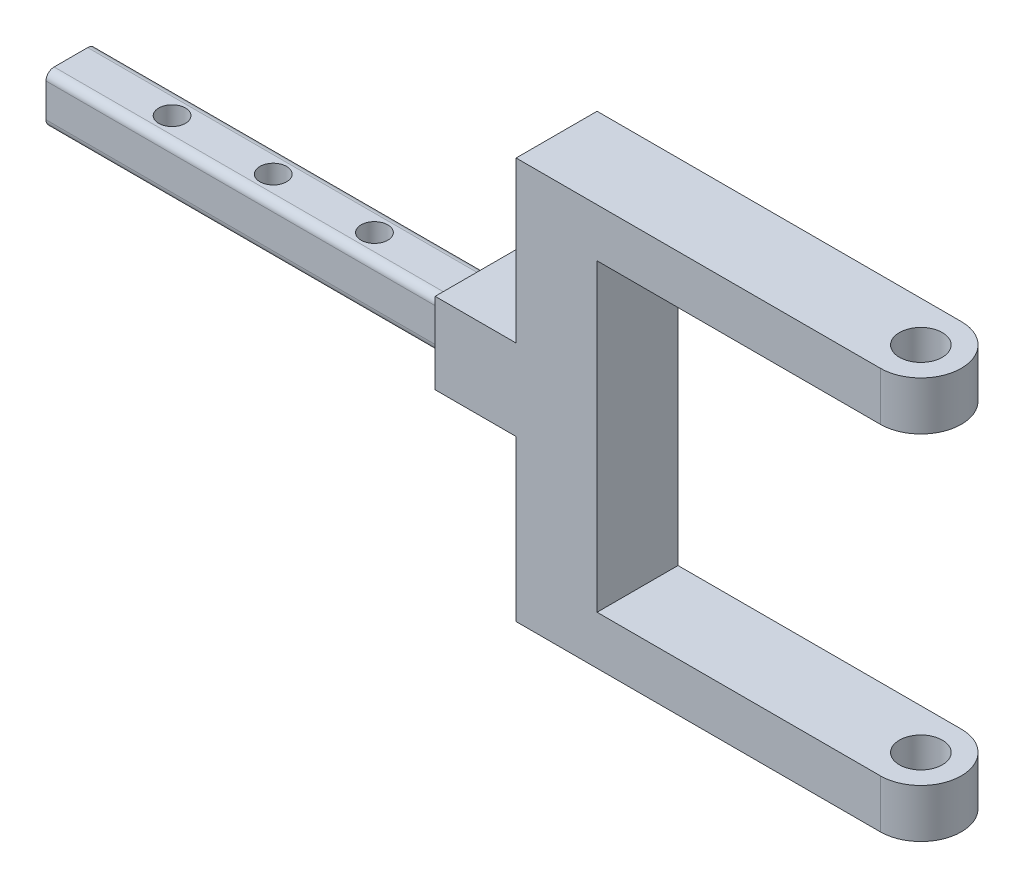
SolidWorks part; units mm, degrees
ref_plane "前视基准面" through (0, 0, 0) normal (0, 0, 1) x (1, 0, 0)
ref_plane "上视基准面" through (0, 0, 0) normal (0, 1, 0) x (1, 0, 0)
ref_plane "右视基准面" through (0, 0, 0) normal (1, 0, 0) x (0, 0, -1)
other "Configuration Table"
sketch "草图1" plane through (0, 0, 0) normal (0, 0, 1) x (1, 0, 0)
  line L0 (0, 18.8) -> (0, -18.8)
  line L1 (0, 18.8) -> (40, 18.8)
  line L2 (40, 18.8) -> (40, 24.8)
  line L3 (40, 24.8) -> (-10, 24.8)
  line L4 (-10, 24.8) -> (-10, -24.8)
  line L5 (-10, -24.8) -> (40, -24.8)
  line L6 (40, -24.8) -> (40, -18.8)
  line L7 (40, -18.8) -> (0, -18.8)
  point P4 (0, 0)
  dimension "D1" = 37.6
  dimension "D2" = 40
  dimension "D3" = 6
  dimension "D4" = 10
extrude "凸台-拉伸1" add sketch "草图1" along normal blind 10
sketch "草图2" plane through (-10, 0, 0) normal (-1, 0, 0) x (0, 0, 1)
  line L0 (8.075, 3.075) -> (8.075, -3.075)
  line L1 (1.925, -3.075) -> (8.075, -3.075)
  line L2 (1.925, 3.075) -> (1.925, -3.075)
  line L3 (1.925, 3.075) -> (8.075, 3.075)
  line L4 (5, 24.8) -> (5, -24.8) construction
  line L5 (0, 0) -> (10, 0) construction
  line L7 (0, 5) -> (10, 5)
  line L8 (0, 24.8) -> (0, -24.8)
  line L9 (0, -24.8) -> (10, -24.8)
  line L10 (10, -24.8) -> (10, 24.8)
  line L11 (10, 24.8) -> (0, 24.8)
  line L12 (0, 24.8) -> (0, -24.8)
  line L13 (0, -24.8) -> (10, -24.8)
  line L14 (10, -24.8) -> (10, 24.8)
  line L15 (10, 24.8) -> (0, 24.8)
  line L16 (0, 5) -> (0, -5)
  line L17 (0, -5) -> (10, -5)
  line L18 (10, 5) -> (10, -5)
  line L19 (5, -5) -> (5, 5) construction
  line L20 (0, 0) -> (10, 0) construction
  line L21 (1.5, 3.5) -> (8.5, 3.5) construction
  line L22 (1.5, 3.5) -> (1.5, -3.5) construction
  line L23 (1.5, -3.5) -> (8.5, -3.5) construction
  line L24 (8.5, 3.5) -> (8.5, -3.5) construction
  line L25 (5, -3.5) -> (5, 3.5) construction
  line L26 (1.5, 0) -> (8.5, 0) construction
  point P6 (5, 0)
  point P13 (5, 0)
  line M8 (0, 24.8) -> (0, -24.8)
  dimension "D2" = 10
  dimension "D3" = 1.5
  dimension "D4" = 6.15
  dimension "D1" = 0
extrude "凸台-拉伸2" add sketch "草图2" along normal blind 10 contours L17 L14 L7 L2 L3 L0 L1 M8 | L3 L2 L1 L0 region at (-10, 0, 5) region at (-10, 4.8586, 5)
extrude "凸台-拉伸3" add sketch "草图2<3>" along normal blind 50 from surface contours L3 L2 L1 L0 region at (-10, 0, 5) starting at face at (-20, 0, 5)
sketch "草图2<3>" plane through (-10, 0, 0) normal (-1, 0, 0) x (0, 0, 1) same geometry as "草图2"
sketch "草图3" plane through (0, 24.8, 0) normal (0, 1, 0) x (1, 0, 0)
  line L0 (-10, -5) -> (40, -5) construction
  line L1 (-10, 0) -> (-10, -10) construction
  line L2 (40, -10) -> (40, 0) construction
  line L3 (40, 0) -> (-10, 0) construction
  circle A0 centre (35, -5) radius 5
  circle A1 centre (35, -5) radius 2.65
  line M1 (40, 0) -> (-10, 0)
  line M3 (-10, -10) -> (40, -10)
  line M4 (40, -10) -> (40, 0)
  dimension "D1" = 5.3
extrude "切除-拉伸1" cut sketch "草图3" against normal through all contours A1 L0 | L0 A1 | A0 M4 M1 | A0 M3 M4 region at (35, 24.8, 6.1247) region at (35, 24.8, 3.8753) region at (38.8832, 24.8, 8.8832) region at (38.8832, 24.8, 1.1168)
sketch "草图4" plane through (0, 3.075, 0) normal (0, 1, 0) x (1, 0, 0)
  line L0 (-70, -5) -> (-20, -5) construction
  line L1 (-70, -8.075) -> (-70, -1.925) construction
  line L2 (-20, 0) -> (-20, -10) construction
  circle A0 centre (-45, -5) radius 1.65
  circle A1 centre (-32.5, -5) radius 1.65
  circle A2 centre (-57.5, -5) radius 1.65
  dimension "D1" = 3.3
  dimension "D2" = 3.3
  dimension "D3" = 3.3
  dimension "D4" = 12.5
  dimension "D5" = 12.5
extrude "切除-拉伸2" cut sketch "草图4" against normal through all
fillet "圆角1" radius 1 4 edges at (-45, 3.075, 8.075) (-45, 3.075, 1.925) (-45, -3.075, 8.075) (-45, -3.075, 1.925)
